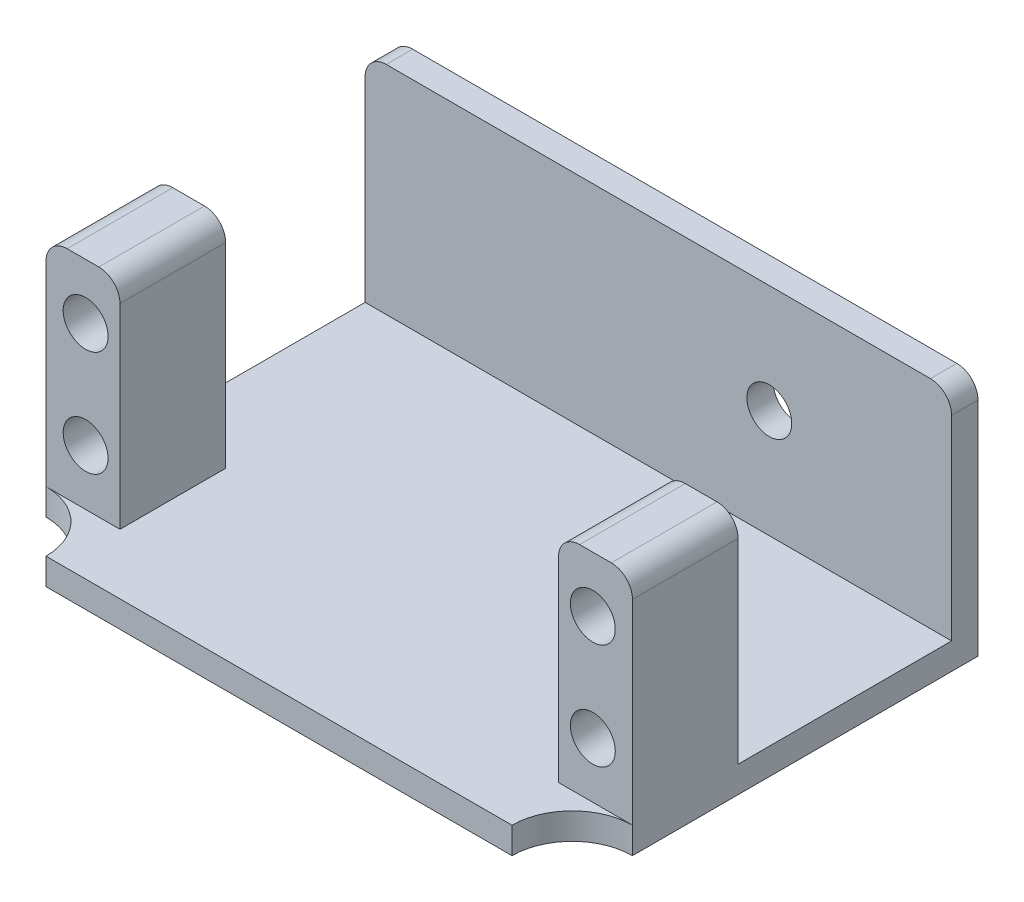
SolidWorks part; units mm, degrees
ref_plane "Front" through (0, 0, 0) normal (0, 0, 1) x (1, 0, 0)
ref_plane "Top" through (0, 0, 0) normal (0, 1, 0) x (1, 0, 0)
ref_plane "Right" through (0, 0, 0) normal (1, 0, 0) x (0, 0, -1)
sketch "Sketch1" plane through (0, 0, 0) normal (0, 1, 0) x (1, 0, 0)
  line L1 (0, 0) -> (55.5, 0)
  line L2 (0, 0) -> (0, 35.9)
  line L3 (0, 35.9) -> (55.5, 35.9)
  line L4 (55.5, 0) -> (55.5, 35.9)
  dimension "D1" = 35.9
  dimension "D2" = 55.5
extrude "bracketBase" add sketch "Sketch1" along normal blind 2.5
ref_plane "referencePlane1" through (0, 0, -8.2) normal (0, 0, 1) x (1, 0, 0)
sketch "Sketch2" plane through (0, 0, -8.2) normal (0, 0, 1) x (1, 0, 0)
  line L0 (27.75, 2.5) -> (27.75, 23) construction
  line L1 (0, 2.5) -> (7, 2.5)
  line L2 (0, 2.5) -> (0, 23)
  line L3 (0, 23) -> (7, 23)
  line L4 (7, 2.5) -> (7, 23)
  line L5 (0, 2.5) -> (55.5, 2.5) construction
  line L6 (55.5, 23) -> (48.5, 23)
  line L7 (48.5, 2.5) -> (48.5, 23)
  line L8 (55.5, 2.5) -> (48.5, 2.5)
  line L9 (55.5, 2.5) -> (55.5, 23)
  dimension "D1" = 20.5
  dimension "D2" = 7
extrude "servoMountingHoleTabs" add sketch "Sketch2" along normal blind 2.5
sketch "Sketch3" plane through (0, 0, -5.7) normal (0, 0, 1) x (1, 0, 0)
  line L0 (0, 12.75) -> (7, 12.75) construction
  line L3 (0, 23) -> (0, 2.5) construction
  line L4 (7, 2.5) -> (7, 23) construction
  line L5 (7, 23) -> (0, 23) construction
  line L6 (27.75, 2.5) -> (27.75, 23) construction
  line L7 (0, 2.5) -> (55.5, 2.5) construction
  circle A0 centre (3.75, 17.75) radius 2.125
  circle A1 centre (3.75, 7.75) radius 2.125
  circle A2 centre (51.75, 7.75) radius 2.125
  circle A3 centre (51.75, 17.75) radius 2.125
  dimension "D1" = 4.25
  dimension "D2" = 3.75
  dimension "D3" = 5.25
extrude "servoMountingHoles" cut sketch "Sketch3" against normal blind 2.5
sketch "Sketch4" plane through (0, 0, 0) normal (0, 1, 0) x (1, 0, 0)
  line L0 (55.5, 8.2) -> (55.5, 35.9) construction
  line L1 (0, 35.9) -> (55.5, 35.9)
  line L2 (0, 35.9) -> (0, 38.4)
  line L3 (0, 38.4) -> (55.5, 38.4)
  line L4 (55.5, 35.9) -> (55.5, 38.4)
  dimension "D1" = 2.5
extrude "baseWall" add sketch "Sketch4" along normal up to surface (23 mm away) up to face at (3.5, 23, -6.95)
sketch "Sketch6" plane through (0, 2.5, 0) normal (0, 1, 0) x (1, 0, 0)
  circle A0 centre (0, 0) radius 5.7
  circle A1 centre (55.5, 0) radius 5.7
extrude "baseTrim" cut sketch "Sketch6" against normal blind 2.5
fillet "Fillet1" radius 2 6 edges at (7, 23, -6.95) (48.5, 23, -6.95) (0, 23, -6.95) (55.5, 23, -6.95) (55.5, 23, -37.15) (0, 23, -37.15)
sketch "Sketch7" plane through (0, 0, -38.4) normal (0, 0, -1) x (-1, 0, 0)
  line L0 (0, 21) -> (0, 0) construction
  line L1 (-55.5, 0) -> (0, 0) construction
  circle A0 centre (-17.25, 12.75) radius 2.125
  dimension "D1" = 4.25
  dimension "D2" = 17.25
  dimension "D3" = 12.75
extrude "M4mountingHole" cut sketch "Sketch7" against normal blind 10
sketch "Sketch8" plane through (0, 0, -38.4) normal (0, 0, -1) x (-1, 0, 0)
  line L0 (-27.75, 23) -> (-27.75, 0) construction
  line L1 (-2, 23) -> (-53.5, 23) construction
  line L2 (-55.5, 0) -> (0, 0) construction
  circle A0 centre (-17.25, 12.75) radius 2.125 construction
  circle A1 centre (-17.25, 12.75) radius 2.125 construction
  circle A2 centre (-38.25, 12.75) radius 2.125
extrude "Cut-Extrude1" cut sketch "Sketch8" against normal blind 10
sketch "Sketch9" plane through (0, 0, -38.4) normal (0, 0, -1) x (-1, 0, 0)
  circle A0 centre (-17.25, 12.75) radius 2.125 construction
  circle A1 centre (-17.25, 12.75) radius 2.125
extrude "Boss-Extrude1" add sketch "Sketch9" against normal up to surface (2.5 mm away) up to face at (36.125, 12.75, -35.9)
sketch "Sketch10" plane through (0, 0, -8.2) normal (0, 0, -1) x (-1, 0, 0)
  line L4 (-48.5, 2.5) -> (-48.5, 21)
  line L5 (-50.5, 23) -> (-53.5, 23)
  line L6 (-55.5, 21) -> (-55.5, 2.5)
  line L7 (-55.5, 2.5) -> (-48.5, 2.5)
  line L8 (-48.5, 2.5) -> (-48.5, 21)
  line L9 (-50.5, 23) -> (-53.5, 23)
  line L10 (-55.5, 21) -> (-55.5, 2.5)
  line L11 (-55.5, 2.5) -> (-48.5, 2.5)
  line L12 (-2, 23) -> (-5, 23)
  line L13 (-7, 21) -> (-7, 2.5)
  line L14 (-7, 2.5) -> (0, 2.5)
  line L15 (0, 2.5) -> (0, 21)
  line L16 (-2, 23) -> (-5, 23)
  line L17 (-7, 21) -> (-7, 2.5)
  line L18 (-7, 2.5) -> (0, 2.5)
  line L19 (0, 2.5) -> (0, 21)
  circle A0 centre (-51.75, 17.75) radius 2.125 construction
  circle A1 centre (-51.75, 17.75) radius 2.125
  arc A2 (-48.5, 21) -> (-50.5, 23) centre (-50.5, 21) ccw
  arc A3 (-53.5, 23) -> (-55.5, 21) centre (-53.5, 21) ccw
  arc A4 (-48.5, 21) -> (-50.5, 23) centre (-50.5, 21) ccw
  arc A5 (-53.5, 23) -> (-55.5, 21) centre (-53.5, 21) ccw
  arc A6 (-5, 23) -> (-7, 21) centre (-5, 21) ccw
  arc A7 (0, 21) -> (-2, 23) centre (-2, 21) ccw
  arc A8 (-5, 23) -> (-7, 21) centre (-5, 21) ccw
  arc A9 (0, 21) -> (-2, 23) centre (-2, 21) ccw
  circle A10 centre (-51.75, 7.75) radius 2.125 construction
  circle A11 centre (-51.75, 7.75) radius 2.125
  circle A12 centre (-3.75, 17.75) radius 2.125 construction
  circle A13 centre (-3.75, 17.75) radius 2.125
  circle A14 centre (-3.75, 7.75) radius 2.125 construction
  circle A15 centre (-3.75, 7.75) radius 2.125
  dimension "D1" = 0
  dimension "D2" = 0
extrude "Boss-Extrude2" add sketch "Sketch10" along normal blind 7.5
